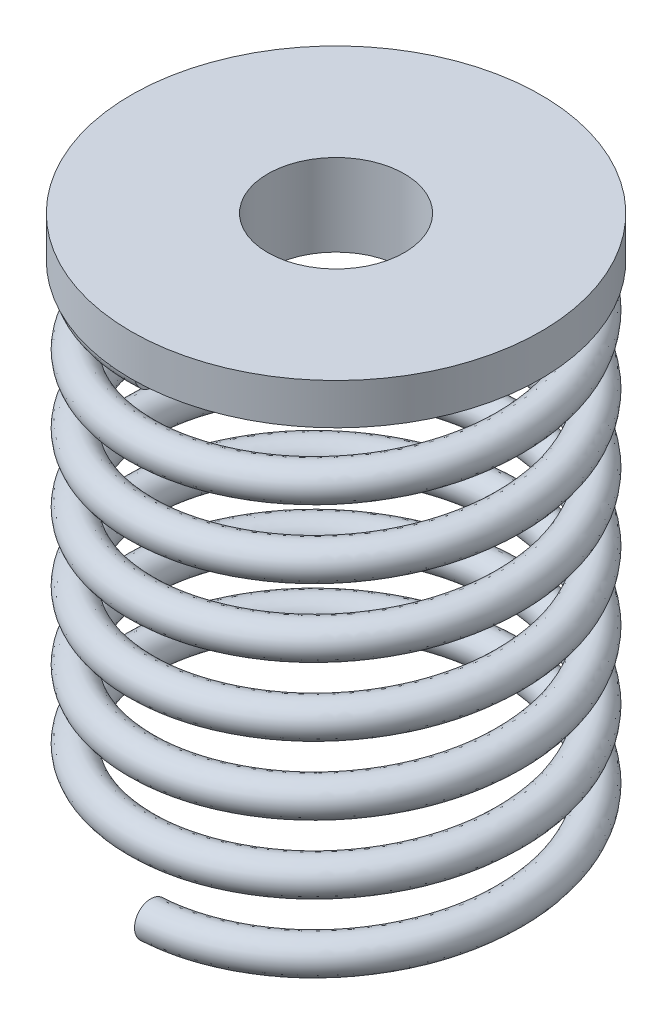
SolidWorks part; units mm, degrees
ref_plane "Front Plane" through (0, 0, 0) normal (0, 0, 1) x (1, 0, 0)
ref_plane "Top Plane" through (0, 0, 0) normal (0, 1, 0) x (1, 0, 0)
ref_plane "Right Plane" through (0, 0, 0) normal (1, 0, 0) x (0, 0, -1)
sketch "Sketch2" plane through (0, 0, 0) normal (0, 1, 0) x (1, 0, 0)
  circle A0 centre (0, 0) radius 15
  dimension "D1" = 30
extrude "Boss-Extrude1" add sketch "Sketch2" along normal blind 3
sketch "Sketch40" plane through (0, 0, 0) normal (0, 1, 0) x (1, 0, 0)
  circle A0 centre (0, 0) radius 13.5
  dimension "D1" = 27
curve "Helix/Spiral2" pitch 5 height 35 turns 7
sweep "Sweep2" add path "Helix/Spiral2" circular profile diameter 2.5 parameters "D3"=2.5
sketch "Sketch55" plane through (0, 3, 0) normal (0, 1, 0) x (1, 0, 0)
  circle A0 centre (0, 0) radius 10
  dimension "D1" = 20
extrude "Boss-Extrude5" add sketch "Sketch55" against normal blind 6
sketch "Sketch56" plane through (0, 3, 0) normal (0, 1, 0) x (1, 0, 0)
  circle A0 centre (0, 0) radius 5
  dimension "D1" = 10
extrude "Cut-Extrude2" cut sketch "Sketch56" against normal blind 9
